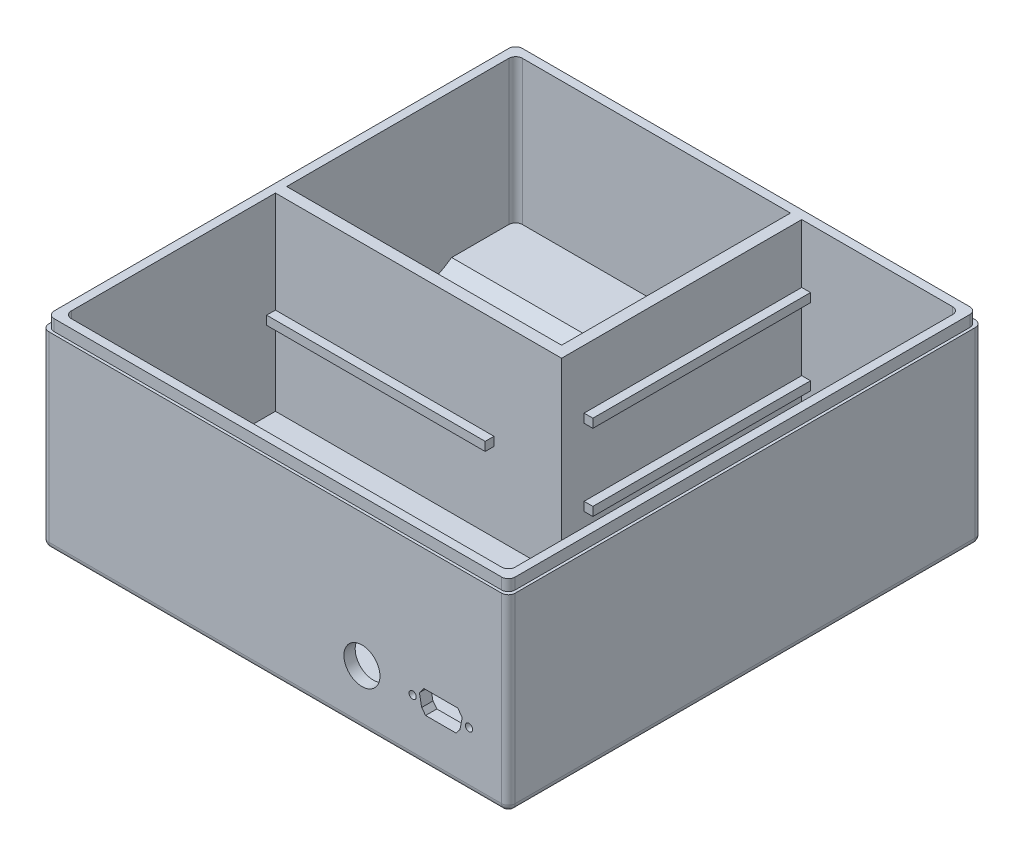
SolidWorks part; units mm, degrees
ref_plane "Plan de face" through (0, 0, 0) normal (0, 0, 1) x (1, 0, 0)
ref_plane "Plan de dessus" through (0, 0, 0) normal (0, 1, 0) x (1, 0, 0)
ref_plane "Plan de droite" through (0, 0, 0) normal (1, 0, 0) x (0, 0, -1)
sketch "Esquisse1" plane through (0, 0, 0) normal (0, 1, 0) x (1, 0, 0)
  line L1 (-103.5, -105.1) -> (103.5, -105.1)
  line L2 (-103.5, -105.1) -> (-103.5, 105.1)
  line L3 (-103.5, 105.1) -> (103.5, 105.1)
  line L4 (103.5, -105.1) -> (103.5, 105.1)
  line L5 (-103.5, -105.1) -> (103.5, 105.1) construction
  line L6 (-103.5, 105.1) -> (103.5, -105.1) construction
  point P0 (0, 0)
  dimension "D1" = 207
  dimension "D2" = 210.2
extrude "Boss.-Extru.1" add sketch "Esquisse1" along normal blind 88.9
shell "Coque1" thickness 5 removed face at (0, 88.9, 0)
sketch "Esquisse2" plane through (-98.5, 0, 0) normal (1, 0, 0) x (0, 0, -1)
  line L0 (105.1, 88.9) -> (105.1, 0) construction
  line L1 (55, 0) -> (-55, 0) construction
  line L2 (105.1, 0) -> (-105.1, 0) construction
  line L3 (89.698, 25) -> (100.1, 25)
  line L4 (49.3, 5) -> (100.1, 5)
  line L5 (100.1, 5) -> (100.1, 25)
  line L6 (49.3, 5) -> (-1.5, 5)
  line L7 (-1.5, 5) -> (-1.5, 25)
  line L8 (-1.5, 25) -> (8.902, 25)
  arc A0 (8.902, 25) -> (89.698, 25) centre (49.3, 55.8) ccw
  dimension "D1" = 101.6
  dimension "D2" = 55.8
  dimension "D3" = 55.8
  dimension "D4" = 25
  dimension "D5" = 10.402
extrude "Boss.-Extru.4" add sketch "Esquisse2" along normal blind 41 from offset 73 contours A0 L8 L7 L3 | A0 L3 L5 region at (-98.5, 12.693, -11.7186) region at (-98.5, 12.693, -86.8814)
sketch "Esquisse3" plane through (15.5, 0, 0) normal (1, 0, 0) x (0, 0, -1)
  line L0 (105.1, 88.9) -> (105.1, 0) construction
  line L1 (-1.5, 5) -> (-1.5, 25)
  line L2 (55, 0) -> (-55, 0) construction
  line L3 (44.2, 5) -> (100.1, 5)
  line L4 (100.1, 5) -> (100.1, 25)
  line L5 (100.1, 25) -> (71.727, 25)
  line L6 (44.2, 5) -> (-1.5, 5)
  line L7 (-1.5, 25) -> (26.873, 25)
  arc A0 (26.873, 25) -> (71.727, 25) centre (49.3, 55.8) ccw
  dimension "D1" = 76.2
  dimension "D2" = 55.8
  dimension "D3" = 55.8
  dimension "D4" = 5
  dimension "D5" = 25
  dimension "D6" = 5
extrude "Boss.-Extru.5" add sketch "Esquisse3" against normal blind 73 from offset 41 contours L7 A0 L5 L4 L3 L6 L1 offset against normal yes
sketch "Esquisse4" plane through (0, 0, 1.5) normal (0, 0, 1) x (1, 0, 0)
  line L0 (-103.5, 88.9) -> (-103.5, 0) construction
  line L1 (23.5, 5) -> (-98.5, 5)
  line L2 (23.5, 5) -> (23.5, 88.9)
  line L3 (23.5, 88.9) -> (-98.5, 88.9)
  line L4 (-98.5, 5) -> (-98.5, 88.9)
  dimension "D1" = 5
  dimension "D2" = 83.9
  dimension "D3" = 122
extrude "Boss.-Extru.6" add sketch "Esquisse4" along normal blind 5
sketch "Esquisse6" plane through (23.5, 0, 0) normal (1, 0, 0) x (0, 0, -1)
  line L0 (-105.1, 0) -> (105.1, 0) construction
  line L1 (-6.5, 88.9) -> (100.1, 88.9)
  line L2 (-6.5, 88.9) -> (-6.5, 5)
  line L3 (-6.5, 5) -> (100.1, 5)
  line L4 (100.1, 88.9) -> (100.1, 5)
  line L5 (105.1, 88.9) -> (105.1, 0) construction
  dimension "D1" = 5
  dimension "D2" = 5
extrude "Boss.-Extru.8" add sketch "Esquisse6" along normal blind 5
sketch "Esquisse9" plane through (-98.5, 0, 0) normal (1, 0, 0) x (0, 0, -1)
  line L0 (-6.5, 88.9) -> (-6.5, 5) construction
  line L1 (-6.5, 40) -> (-10.4, 40)
  line L2 (-6.5, 40) -> (-6.5, 43.9)
  line L3 (-6.5, 43.9) -> (-10.4, 43.9)
  line L4 (-10.4, 40) -> (-10.4, 43.9)
  line L5 (-100.1, 88.9) -> (-100.1, 5) construction
  line L6 (-100.1, 40) -> (-96.2, 40)
  line L7 (-100.1, 40) -> (-100.1, 43.9)
  line L8 (-100.1, 43.9) -> (-96.2, 43.9)
  line L9 (-96.2, 40) -> (-96.2, 43.9)
  line L10 (-105.1, 0) -> (105.1, 0) construction
  point P12 (-98.15, 40)
  dimension "D1" = 40
  dimension "D2" = 3.9
  dimension "D3" = 3.9
extrude "Boss.-Extru.9" add sketch "Esquisse9" along normal offset from surface (97 mm away) 30 up to face at (28.5, 46.95, -46.8)
sketch "Esquisse12" plane through (0, 0, -100.1) normal (0, 0, 1) x (1, 0, 0)
  line L0 (98.5, 88.9) -> (98.5, 5) construction
  line L1 (98.5, 25) -> (94.6, 25)
  line L2 (98.5, 25) -> (98.5, 28.9)
  line L3 (98.5, 28.9) -> (94.6, 28.9)
  line L4 (94.6, 25) -> (94.6, 28.9)
  line L5 (28.5, 5) -> (28.5, 88.9) construction
  line L6 (98.5, 58.9) -> (94.6, 58.9)
  line L7 (98.5, 58.9) -> (98.5, 62.8)
  line L8 (98.5, 62.8) -> (94.6, 62.8)
  line L9 (94.6, 58.9) -> (94.6, 62.8)
  line L10 (28.5, 58.9) -> (32.4, 58.9)
  line L11 (28.5, 58.9) -> (28.5, 62.8)
  line L12 (28.5, 62.8) -> (32.4, 62.8)
  line L13 (32.4, 58.9) -> (32.4, 62.8)
  line L14 (-103.5, 0) -> (103.5, 0) construction
  line L15 (28.5, 25) -> (32.4, 25)
  line L16 (28.5, 25) -> (28.5, 28.9)
  line L17 (28.5, 28.9) -> (32.4, 28.9)
  line L18 (32.4, 25) -> (32.4, 28.9)
  dimension "D1" = 25
  dimension "D2" = 3.9
  dimension "D3" = 3.9
  dimension "D4" = 30
extrude "Boss.-Extru.10" add sketch "Esquisse12" along normal offset from surface (96.6 mm away) 10 up to face at (-42.5, 44.45, 6.5)
sketch "Esquisse14" plane through (0, 88.9, 0) normal (0, 1, 0) x (1, 0, 0)
  line L1 (-103.5, 105.1) -> (103.5, 105.1)
  line L2 (-103.5, 105.1) -> (-103.5, -105.1)
  line L3 (-103.5, -105.1) -> (103.5, -105.1)
  line L4 (103.5, 105.1) -> (103.5, -105.1)
  line L5 (-102.3, 103.9) -> (102.3, 103.9)
  line L6 (-102.3, 103.9) -> (-102.3, -103.9)
  line L7 (-102.3, -103.9) -> (102.3, -103.9)
  line L8 (102.3, 103.9) -> (102.3, -103.9)
  dimension "D1" = 1.2
  dimension "D2" = 1.2
  dimension "D3" = 1.2
  dimension "D4" = 1.2
extrude "Enlèv. mat.-Extru.1" cut sketch "Esquisse14" against normal blind 5
fillet "Congé1" radius 3 16 edges at (-103.5, 41.95, -105.1) (-103.5, 41.95, 105.1) (-103.5, 0, 0) (103.5, 41.95, -105.1) (0, 0, -105.1) (103.5, 0, 0) (0, 0, 105.1) (103.5, 41.95, 105.1) (98.5, 46.95, 100.1) (98.5, 75.85, -100.1) (-98.5, 56.95, -100.1) (-98.5, 66.4, 100.1) (-102.3, 86.4, -103.9) (102.3, 86.4, -103.9) (102.3, 86.4, 103.9) (-102.3, 86.4, 103.9)
sketch "Esquisse15" plane through (0, 0, 105.1) normal (0, 0, 1) x (1, 0, 0)
  line L0 (66.75, 20) -> (80.25, 20)
  line L1 (80.25, 20) -> (82, 22.2)
  line L2 (82, 22.2) -> (83, 27.4)
  line L3 (83, 27.4) -> (81, 30)
  line L4 (81, 30) -> (66, 30)
  line L5 (66, 30) -> (64, 27.4)
  line L6 (64, 27.4) -> (65, 22.2)
  line L7 (65, 22.2) -> (66.75, 20)
  line L8 (64, 27.4) -> (83, 27.4) construction
  line L9 (65, 22.2) -> (82, 22.2) construction
  line L10 (61, 25) -> (86, 25) construction
  line L11 (100.5, 0) -> (-100.5, 0) construction
  line L12 (103.5, 83.9) -> (103.5, 3) construction
  line L13 (73.5, 20) -> (73.5, 22.2) construction
  line L14 (73.5, 22.2) -> (73.5, 25) construction
  line L15 (73.5, 25) -> (73.5, 27.4) construction
  line L16 (73.5, 27.4) -> (73.5, 30) construction
  circle A0 centre (86, 25) radius 1.6
  circle A1 centre (61, 25) radius 1.6
  circle A2 centre (38.5, 25) radius 8
  point P9 (73.5, 20)
  dimension "D10" = 3.2
  dimension "D11" = 3.2
  dimension "D14" = 16
  dimension "D1" = 15
  dimension "D2" = 19
  dimension "D3" = 13.5
  dimension "D4" = 17
  dimension "D5" = 2.2
  dimension "D6" = 7.4
  dimension "D7" = 10
  dimension "D8" = 25
  dimension "D9" = 5
  dimension "D12" = 25
  dimension "D13" = 30
  dimension "D15" = 35
extrude "Enlèv. mat.-Extru.2" cut sketch "Esquisse15" against normal up to next
